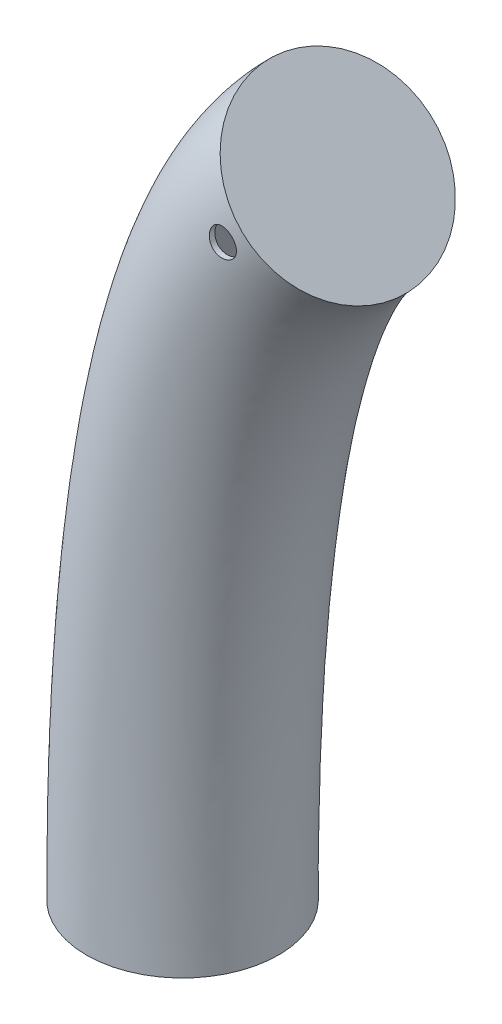
SolidWorks part; units mm, degrees
ref_plane "Plan de face" through (0, 0, 0) normal (0, 0, 1) x (1, 0, 0)
ref_plane "Plan de dessus" through (0, 0, 0) normal (0, 1, 0) x (1, 0, 0)
ref_plane "Plan de droite" through (0, 0, 0) normal (1, 0, 0) x (0, 0, -1)
sketch "Esquisse1" plane through (0, 0, 0) normal (0, 0, 1) x (1, 0, 0)
  line L0 (0, 0) -> (0, 100) construction
  line L1 (0, 100) -> (28.2843, 128.2843) construction
  line L2 (0, 100) -> (54.1696, 100) construction
  line L3 (0, 0) -> (0, 100) construction
  line L4 (0, 100) -> (28.2843, 128.2843) construction
  spline S0 degree 2 poles (0, 0) (0, 100) (28.2843, 128.2843) knots 0 0 0 1 1 1
  dimension "D1" = 100
  dimension "D2" = 45
  dimension "D3" = 40
sketch "Esquisse2" plane through (0, 0, 0) normal (0, 1, 0) x (1, 0, 0)
  circle A0 centre (0, 0) radius 17.5
  circle A2 centre (0, 0) radius 16.5
  dimension "D1" = 1
  dimension "D2" = 35
sweep "Balayage1" add profiles "Esquisse2" path "Esquisse1"
sketch "Esquisse5" plane through (0, 0, 0) normal (0, -1, 0) x (1, 0, 0)
  line L0 (-17, 0) -> (0, 0) construction
  circle A0 centre (-9.5, 0) radius 3.75
  circle A4 centre (0, 0) radius 17
  circle A5 centre (0, 0) radius 17.5 construction
  dimension "D1" = 0.5
  dimension "D3" = 7.5
  dimension "D2" = 7.5
extrude "Boss.-Extru.5" add sketch "Esquisse5" against normal blind 1
sketch "Esquisse6" plane through (0, 0, 0) normal (0, 0, 1) x (1, 0, 0)
  line L0 (15.9099, 140.6586) -> (40.6586, 115.9099) construction
  line L1 (24.7487, 124.7487) -> (28.2843, 128.2843) construction
  circle A0 centre (24.7487, 124.7487) radius 2.5
  point P6 (28.2843, 128.2843)
  dimension "D2" = 5
  dimension "D1" = 5
extrude "Enlèv. mat.-Extru.1" cut sketch "Esquisse6" against normal through all both and the other way through all
sketch "Esquisse7" plane through (78.2843, 78.2843, 0) normal (0.7071, 0.7071, 0) x (0, 0, -1)
  circle A0 centre (0, 70.7107) radius 17
  circle A1 centre (0, 70.7107) radius 17.5 construction
  dimension "D1" = 0.5
extrude "Boss.-Extru.6" add sketch "Esquisse7" against normal blind 1
